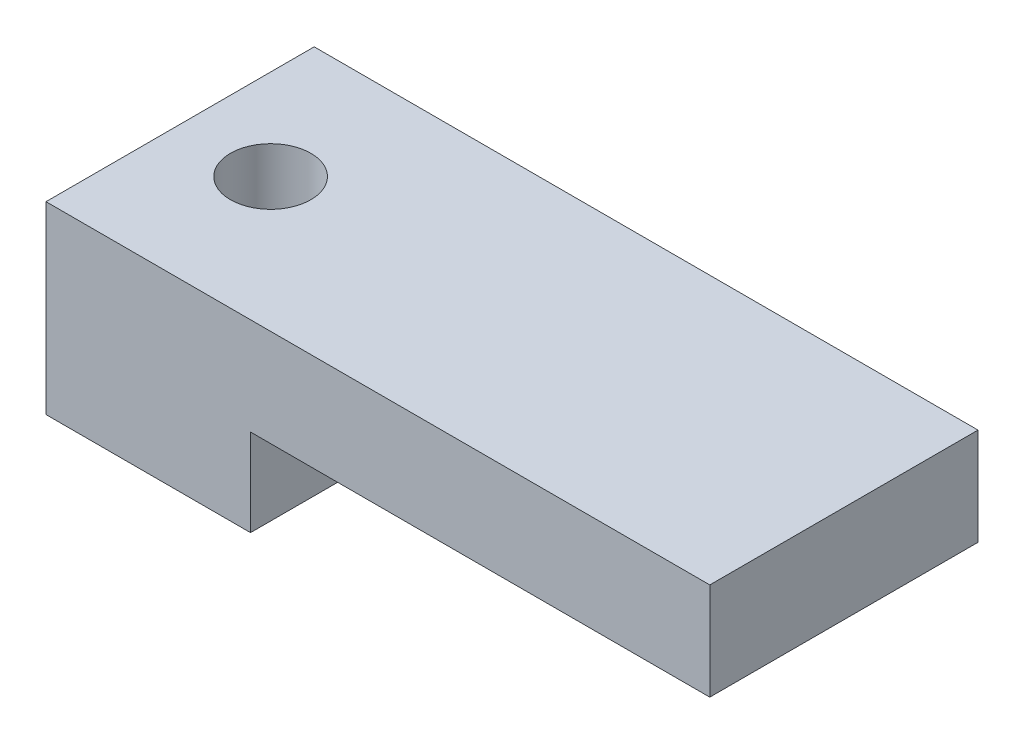
SolidWorks part; units mm, degrees
ref_plane "Front Plane" through (0, 0, 0) normal (0, 0, 1) x (1, 0, 0)
ref_plane "Top Plane" through (0, 0, 0) normal (0, 1, 0) x (1, 0, 0)
ref_plane "Right Plane" through (0, 0, 0) normal (1, 0, 0) x (0, 0, -1)
sketch "Sketch1" plane through (0, 0, 0) normal (0, 0, 1) x (1, 0, 0)
  line L4 (0, 0) -> (6.1, 0)
  line L17 (6.1, 2.6) -> (6.1, 0)
  line L21 (6.1, 2.6) -> (19.8, 2.6)
  line L23 (19.8, 5.5) -> (19.8, 2.6)
  line L24 (0, 0) -> (0, 5.5)
  line L25 (19.8, 5.5) -> (0, 5.5)
  point P2 (19.6, 5.5)
  point P3 (19.3835, 5.5)
  dimension "D3" = 6.1
  dimension "D4" = 5.5
  dimension "D6" = 13.7
  dimension "D10" = 2.6
extrude "Boss-Extrude2" add sketch "Sketch1" along normal mid plane 8
sketch "Sketch2" plane through (0, 0, 0) normal (0, 1, 0) x (1, 0, 0)
  line L0 (0, 0) -> (2.7, 0) construction
  line L1 (0, -4) -> (0, 4) construction
  circle A0 centre (2.7, 0) radius 1.2
  dimension "D1" = 2.4
  dimension "D2" = 2.7
extrude "Cut-Extrude2" cut sketch "Sketch2" against normal through all and the other way through all
